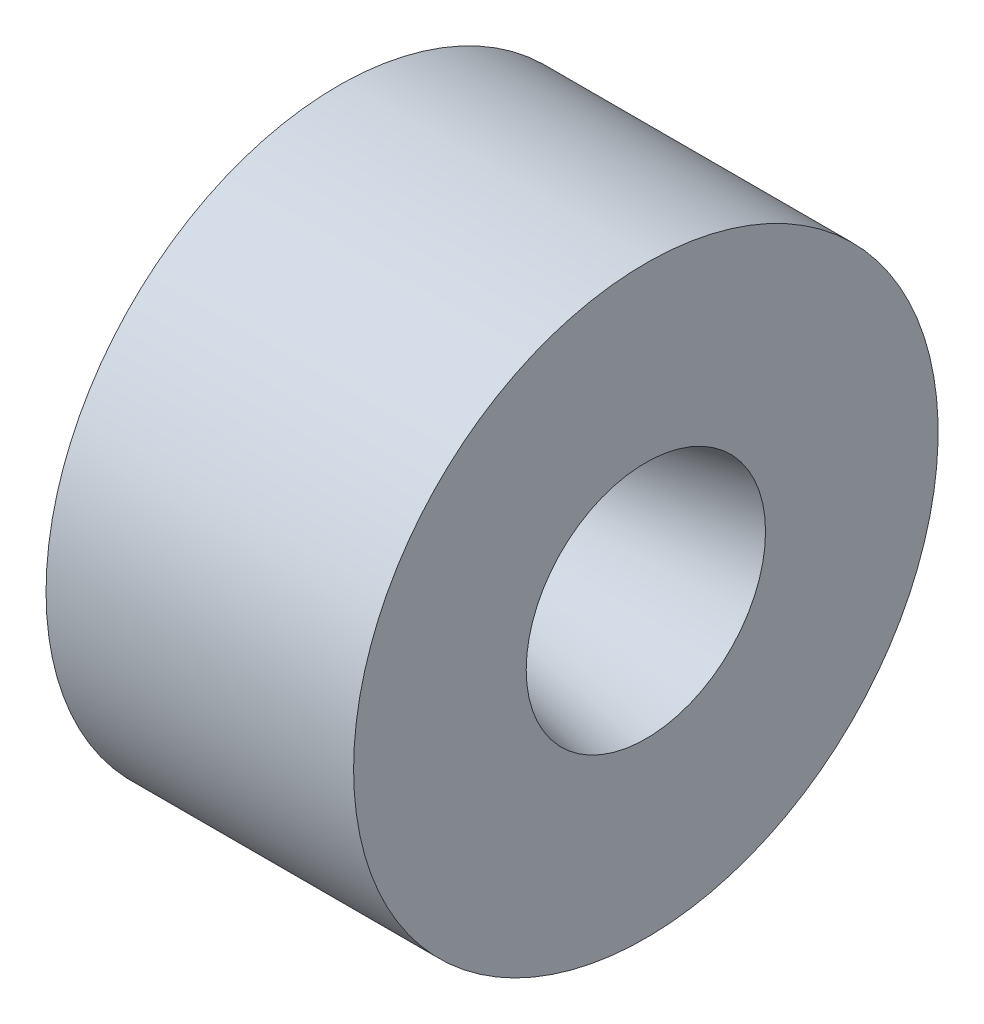
SolidWorks part; units mm, degrees
ref_plane "Front Plane" through (0, 0, 0) normal (0, 0, 1) x (1, 0, 0)
ref_plane "Top Plane" through (0, 0, 0) normal (0, 1, 0) x (1, 0, 0)
ref_plane "Right Plane" through (0, 0, 0) normal (1, 0, 0) x (0, 0, -1)
sketch "Sketch1" plane through (0, 0, 0) normal (0, 0, 1) x (1, 0, 0)
  line L1 (0, -139.7) -> (-73.5, -139.7)
  line L2 (-73.5, -139.7) -> (-73.5, -57.2)
  line L4 (-13.5, -41.25) -> (-13.5, -20)
  line L6 (-62.8571, 0) -> (53.4694, 0) construction
  line L7 (0, -139.7) -> (73.5, -139.7)
  line L8 (73.5, -139.7) -> (73.5, -57.2)
  line L9 (73.5, -57.2) -> (-5.499, -41.25)
  line L10 (-5.499, -41.25) -> (-5.499, -20)
  line L12 (-13.5, -20) -> (-5.499, -20)
  line L13 (-73.5, -57.2) -> (-13.5, -41.25)
  point P5 (-13.6011, -41.2132)
  point P7 (-5.499, -41.25)
  dimension "D1" = 20
  dimension "D2" = 139.7
  dimension "D3" = 41.25
  dimension "D4" = 147
  dimension "D5" = 60
  dimension "D6" = 8.001
  dimension "D7" = 82.5
  dimension "D8" = 82.5
revolve "Revolve1" add sketch "Sketch1" angle 360 about L6
hole_wizard "M8 Clearance Hole1" positions "Sketch5" profile "Sketch4" hole size "M8" standard "ANSI Metric" end condition through all
sketch "Sketch5" plane through (-13.5, 0, 0) normal (-1, 0, 0) x (0, 0, 1)
  circle A0 centre (0, 0) radius 29
  point P5 (0, -29)
  point P12 (-25.1147, 14.5)
  point P13 (25.1147, 14.5)
  dimension "D1" = 58
  dimension "D2" = 3
sketch "Sketch4" plane through (-13.5, 14.5, 25.1147) normal (0, 1, 0) x (0, 0, 1)
  line L0 (0, 0) -> (0, 87)
  line L1 (0, 87) -> (5, 87)
  line L2 (5, 87) -> (5, 0)
  line L5 (5, 0) -> (0, 0)
  line L11 (0, -6.35) -> (0, 107.95) construction
  dimension "Thru Hole Dia." = 10
  dimension "Thru Hole Depth" = 87
